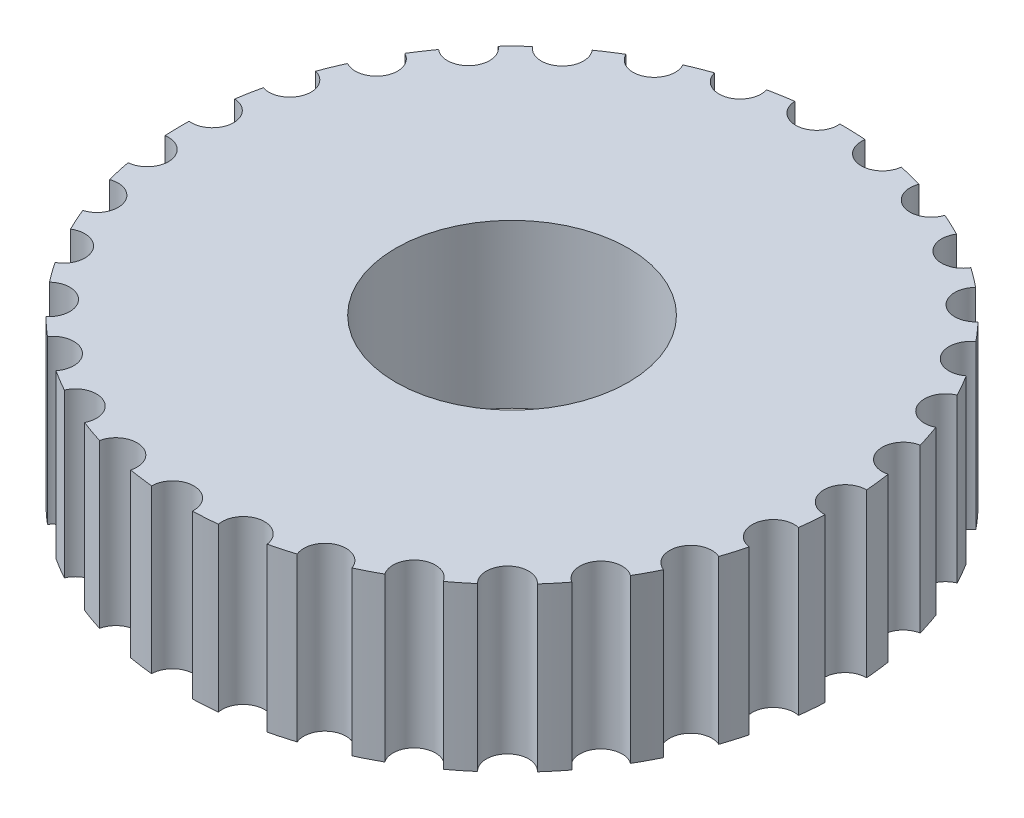
SolidWorks part; units mm, degrees
other "Markup1"
sketch "Sketch4" plane through (-20.25, 10, -20.25) normal (0, 1, 0) x (1, 0, 0)
ref_plane "Front Plane" through (0, 0, 0) normal (0, 0, 1) x (1, 0, 0)
ref_plane "Top Plane" through (0, 0, 0) normal (0, 1, 0) x (1, 0, 0)
ref_plane "Right Plane" through (0, 0, 0) normal (1, 0, 0) x (0, 0, -1)
sketch "Sketch1" plane through (0, 0, 0) normal (0, 1, 0) x (1, 0, 0)
  circle A1 centre (0, 0) radius 20.25
  dimension "D2" = 40.5
extrude "Boss-Extrude1" add sketch "Sketch1" along normal blind 10 contours A1
sketch "Sketch3" plane through (0, 10, 0) normal (0, 1, 0) x (1, 0, 0)
  line L0 (0, 0) -> (0, 20.25) construction
  circle A0 centre (0, 0) radius 20.25 construction
  circle A1 centre (0, 0) radius 20.25 construction
  arc A2 (0, 20.25) -> (1.499, 20.1944) centre (-0.0063, -0.1695) cw
  arc A3 (1.499, 20.1944) -> (4.073, 19.8362) centre (2.7807, 19.9775) ccw
  arc A4 (1.499, 20.1944) -> (4.073, 19.8362) centre (0.0133, 0.0957) cw
  circle M4 centre (0, 0) radius 20.25
  dimension "D2" = 1.3
  dimension "D1" = 1.5
extrude "Cut-Extrude2" cut sketch "Sketch3" against normal through all contours A3 M4 region at (2.7096, 10, -19.4663)
pattern_circular "CirPattern2" count 31 every 11.604 about axis through (0, 10, 0) along (0, -1, 0) of "Cut-Extrude2"
hole_wizard "Ø1.0mm Dowel Hole1" positions "Sketch5" profile "Sketch6" hole size "Ø1.0" standard "ISO" end condition through all
sketch "Sketch5" plane through (0, 10, 0) normal (0, 1, 0) x (1, 0, 0)
  point P0 (0, 0)
sketch "Sketch6" plane through (0, 10, 0) normal (1, 0, 0) x (0, 0, 1)
  line L0 (0, 0) -> (0, 10)
  line L1 (0, 10) -> (7.1437, 10)
  line L2 (7.1437, 10) -> (7.1437, 0)
  line L5 (7.1437, 0) -> (0, 0)
  line L11 (0, -6.35) -> (0, 107.95) construction
  dimension "Thru Hole Dia." = 14.2875
  dimension "Thru Hole Depth" = 10
equation "\"D2@Sketch1\"=\"diameter\""
equation "\"diameter\"= 40.5'The diameter of the outer circle."
equation "\"numInstances\"= pi * \"diameter\" / \"patternArcLength\"'The number of pattern instances required to fill the outer circle. Gotten by adjusting the diameter so that I could get close to an integer number of instances."
equation "\"patternArcLength\"= \"D3@Sketch3\"'The arc length of the bead gear teeth pattern that I measured from the original stock part that came with my blind."
equation "\"D1@CirPattern2\"=int( \"numInstances\")"
equation "\"D2@CirPattern2\"= 360 / \"numInstances\""
